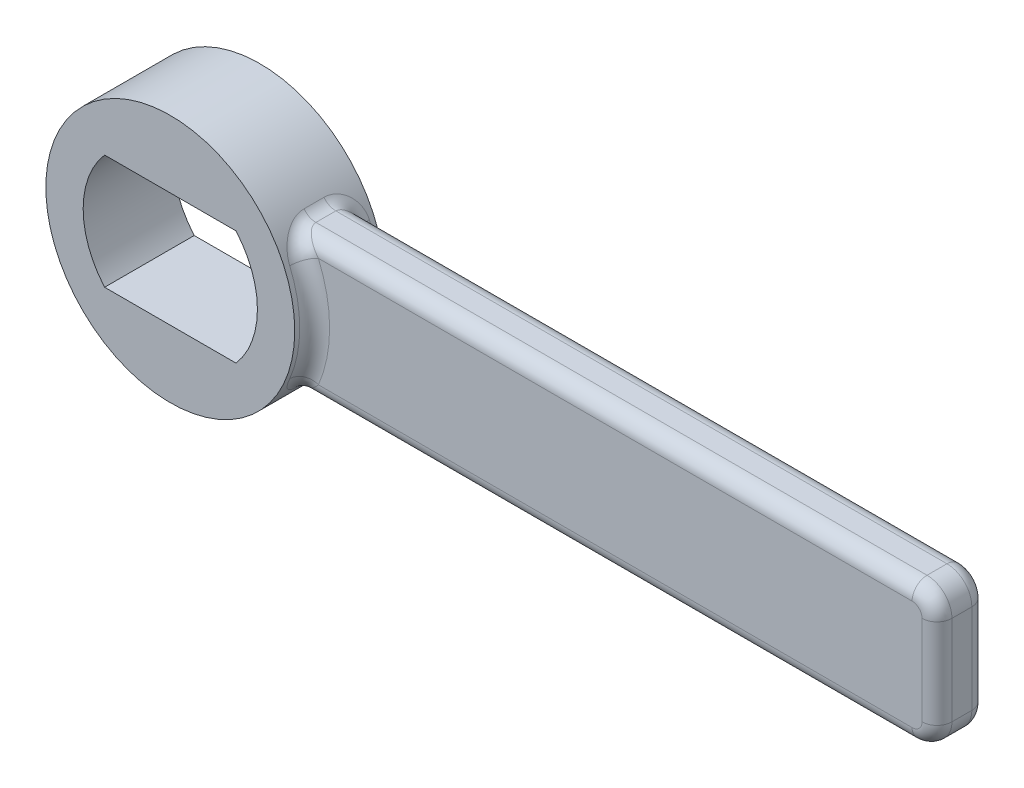
SolidWorks part; units mm, degrees
material "Сталь 40Х13 ГОСТ 5632-72"
ref_plane "Спереди" through (0, 0, 0) normal (0, 0, 1) x (1, 0, 0)
ref_plane "Сверху" through (0, 0, 0) normal (0, 1, 0) x (1, 0, 0)
ref_plane "Справа" through (0, 0, 0) normal (1, 0, 0) x (0, 0, -1)
sketch "Эскиз1" plane through (0, 0, 0) normal (0, 0, 1) x (1, 0, 0)
  line L0 (0, 0) -> (25, 0) construction
  line L1 (150, -14) -> (0, -14)
  line L2 (150, -14) -> (150, 14)
  line L3 (150, 14) -> (0, 14)
  line L4 (0, -14) -> (0, 14)
  line L5 (150, -14) -> (0, 14) construction
  line L6 (150, 14) -> (0, -14) construction
  line L8 (-13.1909, 11.5) -> (13.1909, 11.5)
  line L9 (-13.1909, -11.5) -> (13.1909, -11.5)
  circle A0 centre (0, 0) radius 25
  circle A1 centre (0, 0) radius 17.5
  point P3 (75, 0)
  point P8 (0, 0)
  dimension "D1" = 50
  dimension "D4" = 35
  dimension "D2" = 28
  dimension "D3" = 150
  dimension "D5" = 23
extrude "Бобышка-Вытянуть1" add sketch "Эскиз1" along normal mid plane 18 contours A1 L3 A0 L1 | L3 A1 L8 L4 | L8 A1 L3 L4 | L9 A1 L1 L4 | L1 A1 L9 L4 | A1 L1 A0 L3 region at (-24.3225, 0, 0) region at (19.3618, 0, 0) region at (-2.2391, -14.4008, 0) region at (5.9952, -12.7033, 0) region at (5.9952, 12.7033, 0) region at (-2.2391, 14.4008, 0)
extrude "Бобышка-Вытянуть2" add sketch "Эскиз1<5>" along normal mid plane 10 contours A0 L1 L2 L3 region at (86.8056, 0, 0)
sketch "Эскиз1<5>" plane through (0, 0, 0) normal (0, 0, 1) x (1, 0, 0) same geometry as "Эскиз1"
fillet "Скругление3" radius 5 2 edges at (150, 14, 0) (150, -14, 0)
fillet "Скругление4" radius 3 14 edges at (20.7123, 14, 0) (25, 0, 5) (25, 0, -5) (82.8562, 14, -5) (148.5355, 12.5355, -5) (150, 0, -5) (148.5355, -12.5355, -5) (82.8562, 14, 5) (148.5355, 12.5355, 5) (150, 0, 5) (148.5355, -12.5355, 5) (20.7123, -14, 0) (82.8562, -14, -5) (82.8562, -14, 5)
